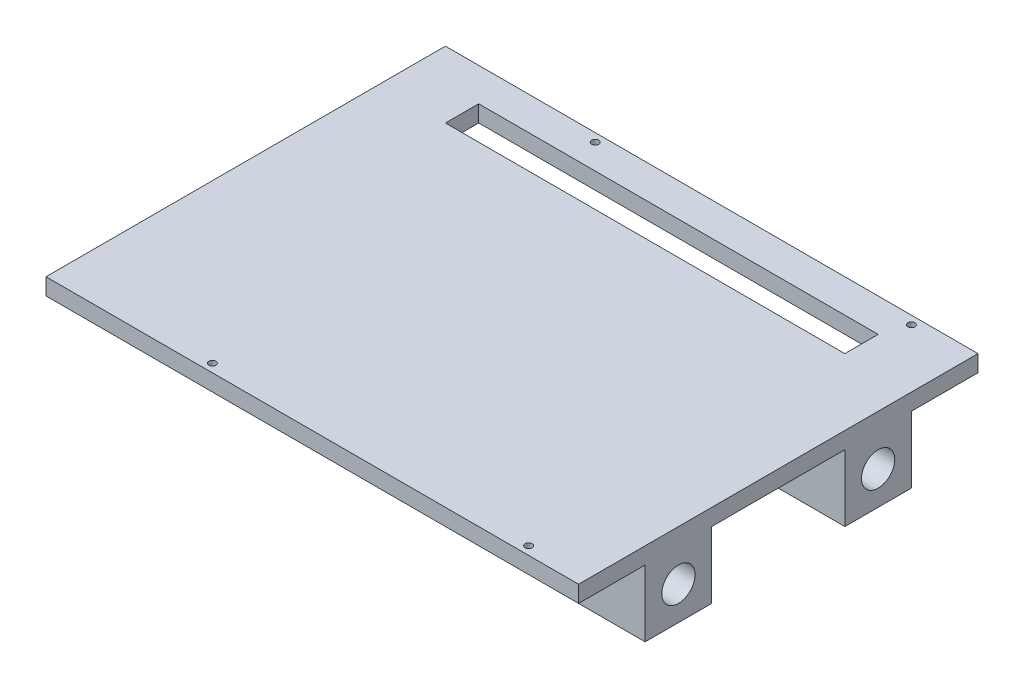
SolidWorks part; units mm, degrees
ref_plane "Front Plane" through (0, 0, 0) normal (0, 0, 1) x (1, 0, 0)
ref_plane "Top Plane" through (0, 0, 0) normal (0, 1, 0) x (1, 0, 0)
ref_plane "Right Plane" through (0, 0, 0) normal (1, 0, 0) x (0, 0, -1)
sketch "Sketch2" plane through (0, 0, 0) normal (0, 1, 0) x (1, 0, 0)
  line L1 (-101.6, -76.2) -> (101.6, -76.2)
  line L2 (-101.6, -76.2) -> (-101.6, 76.2)
  line L3 (-101.6, 76.2) -> (101.6, 76.2)
  line L4 (101.6, -76.2) -> (101.6, 76.2)
  line L5 (-101.6, -76.2) -> (101.6, 76.2) construction
  line L6 (-101.6, 76.2) -> (101.6, -76.2) construction
  point P0 (0, 0)
  dimension "D1" = 203.2
  dimension "D2" = 152.4
extrude "Boss-Extrude1" add sketch "Sketch2" along normal blind 6.35
sketch "Sketch3" plane through (0, 6.35, 0) normal (0, 1, 0) x (1, 0, 0)
  line L0 (-101.6, 0) -> (101.6, 0) construction
  line L1 (-101.6, 76.2) -> (-101.6, -76.2) construction
  line L2 (101.6, -76.2) -> (101.6, 76.2) construction
  line L3 (0, 76.2) -> (0, -76.2) construction
  line L4 (101.6, 76.2) -> (-101.6, 76.2) construction
  line L5 (-101.6, -76.2) -> (101.6, -76.2) construction
  line L7 (-76.2, 63.5) -> (76.2, 63.5)
  line L8 (-76.2, 63.5) -> (-76.2, 50.8)
  line L9 (-76.2, 50.8) -> (76.2, 50.8)
  line L10 (76.2, 63.5) -> (76.2, 50.8)
  line L11 (-76.2, 63.5) -> (76.2, 50.8) construction
  line L12 (-76.2, 50.8) -> (76.2, 63.5) construction
  point P12 (0, 57.15)
  dimension "D1" = 12.7
  dimension "D2" = 152.4
  dimension "D3" = 12.7
extrude "Cut-Extrude1" cut sketch "Sketch3" against normal blind 6.35
sketch "Sketch4" plane through (0, 0, 0) normal (0, -1, 0) x (1, 0, 0)
  line L0 (-101.6, -76.2) -> (-101.6, 76.2) construction
  line L1 (-101.6, 50.8) -> (-50.8, 50.8)
  line L2 (-101.6, 50.8) -> (-101.6, 25.4)
  line L3 (-101.6, 25.4) -> (-50.8, 25.4)
  line L4 (-50.8, 50.8) -> (-50.8, 25.4)
  line L5 (0, 76.2) -> (0, -76.2) construction
  line L6 (-101.6, 76.2) -> (101.6, 76.2) construction
  line L7 (101.6, -76.2) -> (-101.6, -76.2) construction
  line L8 (-101.6, 0) -> (101.6, 0) construction
  line L9 (101.6, 76.2) -> (101.6, -76.2) construction
  line L10 (101.6, 25.4) -> (50.8, 25.4)
  line L11 (50.8, 50.8) -> (50.8, 25.4)
  line L12 (101.6, 50.8) -> (50.8, 50.8)
  line L13 (101.6, 50.8) -> (101.6, 25.4)
  line L14 (101.6, -50.8) -> (101.6, -25.4)
  line L15 (101.6, -50.8) -> (50.8, -50.8)
  line L16 (50.8, -50.8) -> (50.8, -25.4)
  line L17 (101.6, -25.4) -> (50.8, -25.4)
  line L18 (-101.6, -25.4) -> (-50.8, -25.4)
  line L19 (-50.8, -50.8) -> (-50.8, -25.4)
  line L20 (-101.6, -50.8) -> (-50.8, -50.8)
  line L21 (-101.6, -50.8) -> (-101.6, -25.4)
  dimension "D1" = 25.4
  dimension "D2" = 50.8
  dimension "D3" = 25.4
sketch "Sketch6" plane through (0, 0, 0) normal (0, -1, 0) x (1, 0, 0)
  line L0 (0, -50.8) -> (0, -63.5) construction
  line L1 (-76.2, -50.8) -> (76.2, -50.8) construction
  line L2 (76.2, -63.5) -> (-76.2, -63.5) construction
extrude "Boss-Extrude2" add sketch "Sketch4" along normal blind 25.4
sketch "Sketch7" plane through (-101.6, 0, 0) normal (-1, 0, 0) x (0, 0, 1)
  line L0 (-38.1, -25.4) -> (-38.1, 6.35) construction
  line L1 (-25.4, -25.4) -> (-50.8, -25.4) construction
  line L2 (-76.2, 6.35) -> (76.2, 6.35) construction
  line L3 (-50.8, -12.7) -> (-25.4, -12.7) construction
  line L4 (-50.8, -25.4) -> (-50.8, 0) construction
  line L5 (-25.4, -25.4) -> (-25.4, 0) construction
  line L6 (38.1, -25.4) -> (38.1, 6.35) construction
  line L7 (50.8, -25.4) -> (25.4, -25.4) construction
  line L8 (25.4, -12.7) -> (50.8, -12.7) construction
  line L9 (25.4, -25.4) -> (25.4, 0) construction
  line L10 (50.8, -25.4) -> (50.8, 0) construction
  circle A0 centre (-38.1, -12.7) radius 6.35
  circle A1 centre (38.1, -12.7) radius 6.35
  dimension "D1" = 12.7
  dimension "D2" = 12.7
extrude "Cut-Extrude2" cut sketch "Sketch7" against normal blind 50.8
sketch "Sketch8" plane through (101.6, 0, 0) normal (1, 0, 0) x (0, 0, -1)
  line L0 (-50.8, -12.7) -> (50.8, -12.7) construction
  line L1 (-50.8, -25.4) -> (-50.8, 0) construction
  line L2 (50.8, -25.4) -> (50.8, 0) construction
  line L3 (-38.1, -25.4) -> (-38.1, 6.35) construction
  line L4 (50.8, -25.4) -> (25.4, -25.4) construction
  line L5 (38.1, -25.4) -> (38.1, 6.35) construction
  line L6 (-76.2, 6.35) -> (76.2, 6.35) construction
  line L7 (-25.4, -25.4) -> (-50.8, -25.4) construction
  circle A0 centre (-38.1, -12.7) radius 6.35
  circle A1 centre (38.1, -12.7) radius 6.35
  dimension "D1" = 12.7
  dimension "D2" = 12.7
extrude "Cut-Extrude3" cut sketch "Sketch8" against normal blind 50.8
ref_plane "Plane1" through (0, 0, 0) normal (-1, 0, 0) x (0, 0, 1)
ref_point "Point1"
sketch "Sketch12" plane through (0, 6.35, 0) normal (0, 1, 0) x (1, 0, 0)
  line L0 (101.6, 76.2) -> (-101.6, 76.2) construction
  line L1 (-38.1204, 76.2) -> (25.3796, 76.2)
  line L2 (-38.1204, 76.2) -> (-38.1204, 63.5)
  line L3 (-38.1204, 63.5) -> (25.3796, 63.5)
  line L4 (25.3796, 76.2) -> (25.3796, 63.5)
  line L5 (76.2, 63.5) -> (-76.2, 63.5) construction
  dimension "D1" = 63.5
hole_wizard "#6-32 Tapped Hole1" positions "Sketch13" profile "Sketch14" tap size "#6-32" standard "ANSI Inch"
sketch "Sketch13" plane through (0, 6.35, 0) normal (0, 1, 0) x (1, 0, 0)
  point P12 (-41.275, -73.025)
  point P15 (-41.275, 73.025)
  point P18 (79.375, 73.025)
  point P21 (79.375, -73.025)
  point P24 (-41.275, -73.025)
  point P25 (-41.2353, -71.353)
  point P26 (-41.1082, -72.149)
  point P27 (-41.3945, -73.025)
  point P28 (0, 0)
  point P29 (-41.275, -73.025)
  point P30 (79.375, -73.025)
  point P31 (79.375, 73.025)
  point P32 (-41.3431, 72.8968)
  point P33 (-41.275, 73.025)
  point P35 (79.375, 73.025)
  point P37 (79.375, -73.025)
  point P39 (-41.275, -73.025)
cosmetic thread "Hole Thread6"
cosmetic thread "Hole Thread7"
cosmetic thread "Hole Thread8"
cosmetic thread "Hole Thread9"
sketch "Sketch14" plane through (-41.275, 6.35, 73.025) normal (1, 0, 0) x (0, 0, 1)
  line L0 (0, 0) -> (0, 13.5127)
  line L1 (0, 13.5127) -> (1.3525, 12.7)
  line L2 (1.3525, 12.7) -> (1.3525, 0)
  line L5 (1.3525, 0) -> (0, 0)
  line L10 (0, 13.5127) -> (-1.3526, 12.7) construction
  line L11 (0, -6.35) -> (0, 107.95) construction
  dimension "Tap Drill Dia." = 2.7051
  dimension "Tap Drill Depth" = 12.7
  dimension "Drill Angle" = 118
